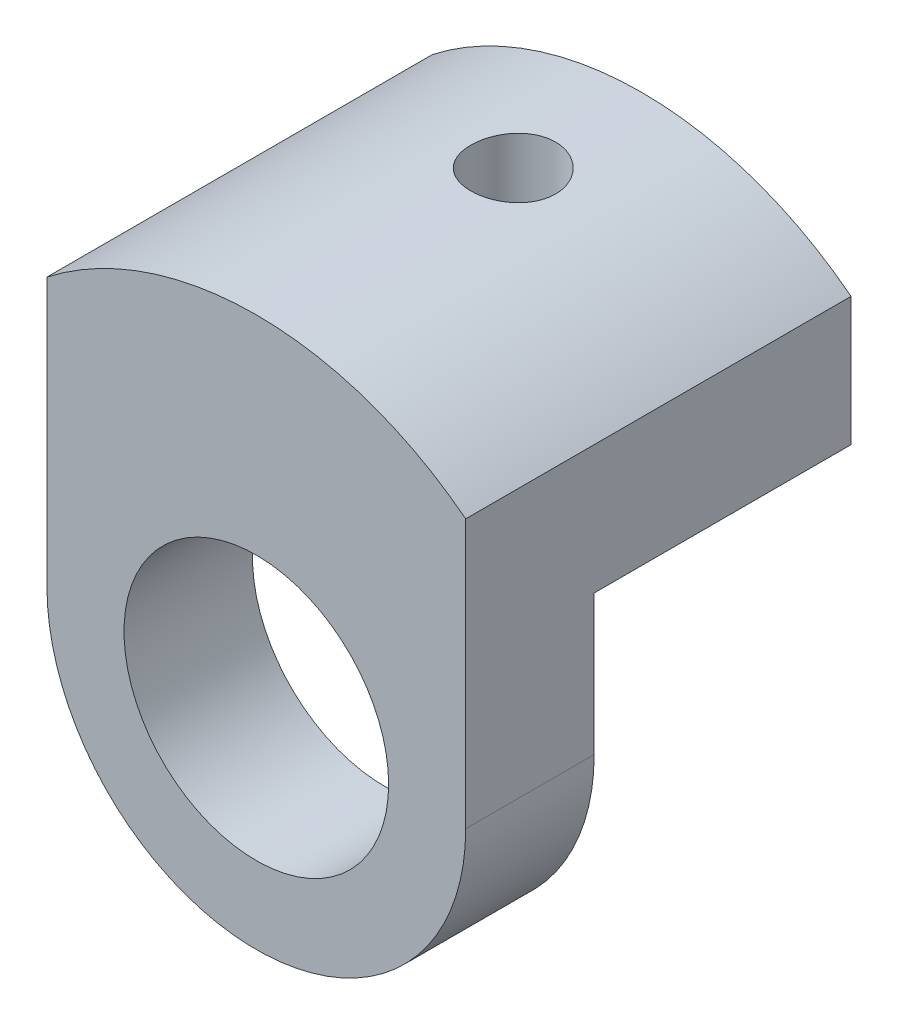
SolidWorks part; units mm, degrees
ref_plane "Front Plane" through (0, 0, 0) normal (0, 0, 1) x (1, 0, 0)
ref_plane "Top Plane" through (0, 0, 0) normal (0, 1, 0) x (1, 0, 0)
ref_plane "Right Plane" through (0, 0, 0) normal (1, 0, 0) x (0, 0, -1)
sketch "Sketch1" plane through (0, 0, 0) normal (0, 0, 1) x (1, 0, 0)
  line L0 (-8.15, 0) -> (8.15, 0)
  line L1 (-8.15, 0) -> (-8.15, 10.447)
  line L2 (8.15, 0) -> (8.15, 10.447)
  line L3 (-8.15, 10.447) -> (8.15, 10.447)
  circle A0 centre (0, 0) radius 5.15
  circle A1 centre (0, 0) radius 13.25
  circle A2 centre (0, 0) radius 8.15
  point P5 (-8.15, 8.6313)
  point P8 (-8.15, 0)
  dimension "D1" = 10.3
  dimension "D2" = 26.5
  dimension "D3" = 3
extrude "Boss-Extrude1" add sketch "Sketch1" along normal blind 5 contours L0 A2 A0 | L0 A2 A0 | A2 L2 L3 L1 | L3 A1 region at (0, 5.3322, 0) region at (6.65, -0.1822, 0) region at (0, 8.3436, 0) region at (0, 11.579, 0)
sketch "Sketch2" plane through (0, 0, 0) normal (0, 0, -1) x (-1, 0, 0)
  line L0 (-8.15, 10.447) -> (8.15, 10.447)
  line L1 (-8.15, 10.447) -> (-8.15, 5.447)
  line L2 (8.15, 10.447) -> (8.15, 5.447)
  line L3 (-8.15, 5.447) -> (8.15, 5.447)
  circle A0 centre (0, 0) radius 13.25
  point P4 (-8.15, 10.447)
  point P7 (8.15, 10.447)
  point P11 (-8.15, 10.447)
  line M7 (8.15, 0) -> (8.15, 10.447)
  arc M8 (8.15, 10.447) -> (-8.15, 10.447) centre (0, 0) ccw
  line M9 (-8.15, 10.447) -> (-8.15, 0)
  dimension "D1" = 5
extrude "Boss-Extrude2" add sketch "Sketch2" along normal blind 10 contours L3 L0 M9 M7 | L0 M8 region at (0, 11.579, 0) region at (0, 7.947, 0)
sketch "Sketch3" plane through (0, 5.447, 0) normal (0, -1, 0) x (1, 0, 0)
  line L0 (8.15, -10) -> (-8.15, -10) construction
  line L1 (-8.15, -10) -> (-8.15, 0) construction
  circle A0 centre (0, -5) radius 1.65
  dimension "D1" = 5
  dimension "D2" = 8.15
  dimension "D3" = 3.3
extrude "Cut-Extrude1" cut sketch "Sketch3" against normal blind 10
sketch "Sketch4" plane through (0, 5.447, 0) normal (0, -1, 0) x (1, 0, 0)
  line L0 (-8.15, -10) -> (-8.15, 0) construction
  line L1 (3, -3.2679) -> (0, -1.5359)
  line L2 (0, -1.5359) -> (-3, -3.2679)
  line L3 (-3, -3.2679) -> (-3, -6.7321)
  line L4 (-3, -6.7321) -> (0, -8.4641)
  line L5 (0, -8.4641) -> (3, -6.7321)
  line L6 (3, -6.7321) -> (3, -3.2679)
  circle A0 centre (0, -5) radius 3 construction
  circle A1 centre (0, -5) radius 1.65 construction
  point P1 (0, 0)
  dimension "D1" = 6
extrude "Cut-Extrude2" cut sketch "Sketch4" against normal blind 2.5
